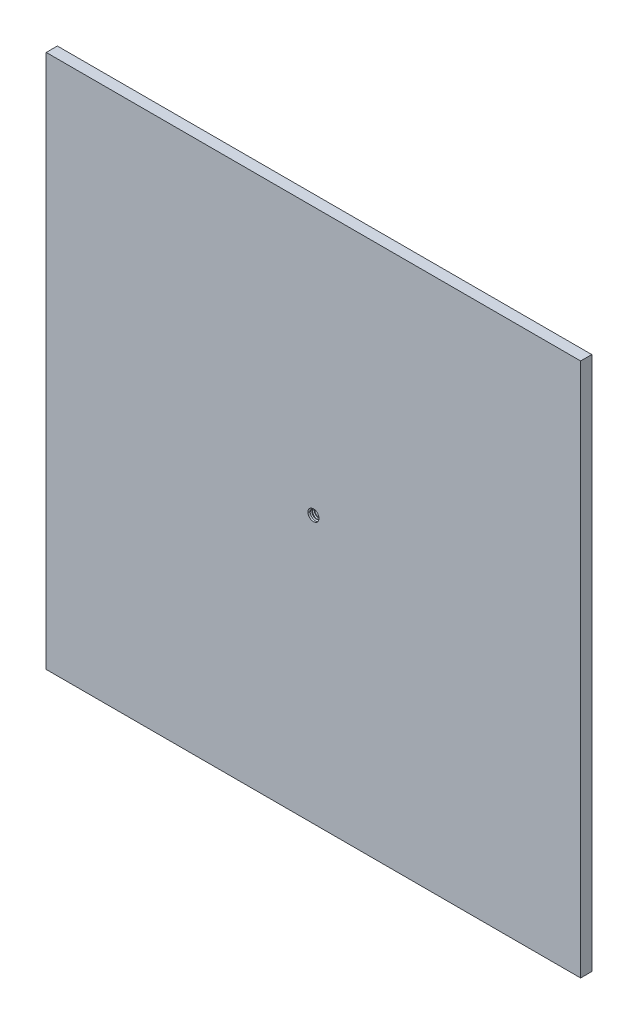
SolidWorks part; units mm, degrees
ref_plane "Front Plane" through (0, 0, 0) normal (0, 0, 1) x (1, 0, 0)
ref_plane "Top Plane" through (0, 0, 0) normal (0, 1, 0) x (1, 0, 0)
ref_plane "Right Plane" through (0, 0, 0) normal (1, 0, 0) x (0, 0, -1)
sketch "Sketch1" plane through (0, 0, 0) normal (0, 0, 1) x (1, 0, 0)
  line L1 (0, 0) -> (304.8, 0)
  line L2 (0, 0) -> (0, 304.8)
  line L3 (0, 304.8) -> (304.8, 304.8)
  line L4 (304.8, 0) -> (304.8, 304.8)
  dimension "D1" = 304.8
  dimension "D2" = 304.8
extrude "Boss-Extrude1" add sketch "Sketch1" along normal blind 6.35
sketch "Sketch2" plane through (0, 0, 6.35) normal (0, 0, 1) x (1, 0, 0)
  circle A0 centre (152.4, 152.4) radius 3.175
extrude "Cut-Extrude1" cut sketch "Sketch2" against normal through all
thread "Thread1" pitch 1.27 method extrude profile "Thread Profile1" start angle 0, offset 0, length 10, pitch 1.27, diameter 6.35
ref_plane "Plane1" through (149.225, 152.4, 6.35) normal (0, -1, 0) x (-1, 0, 0)
sketch "Thread Profile1" plane through (149.225, 152.4, 6.35) normal (0, -1, 0) x (-1, 0, 0)
  line L0 (0, 0) -> (0, 1.27) construction
  line L11 (0, 0) -> (0, 1.1112)
  line L12 (0, 1.1112) -> (-0.6874, 0.7144)
  line L13 (-0.6874, 0.7144) -> (-0.6874, 0.3969)
  line L15 (-0.6874, 0.3969) -> (0, 0)
  line L17 (-0.6874, 0.5556) -> (0, 0.5556) construction
  point P2 (0, 0)
  dimension "Pitch" = 1.27
  dimension "Profile_Angle" = 60
  dimension "Profile_Land" = 0.3175
  dimension "Profile_Height" = 0.6874
